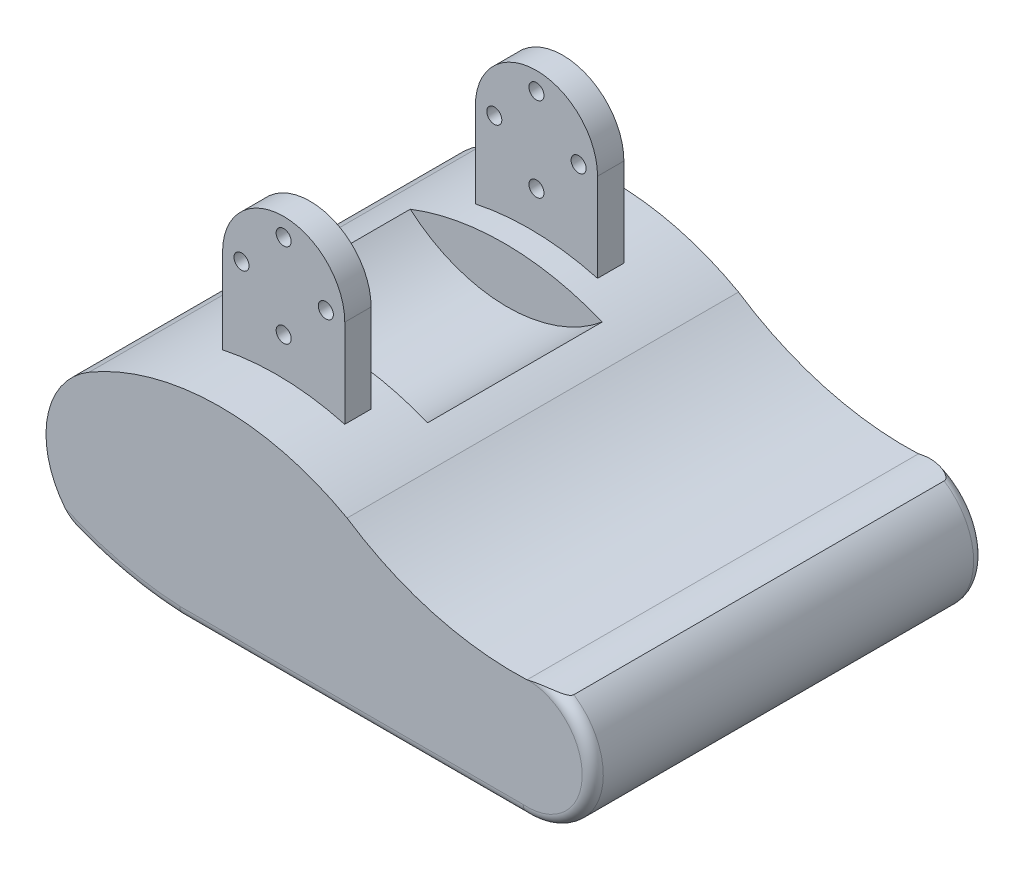
SolidWorks part; units mm, degrees
material "PLA"
ref_plane "Front Plane" through (0, 0, 0) normal (0, 0, 1) x (1, 0, 0)
ref_plane "Top Plane" through (0, 0, 0) normal (0, 1, 0) x (1, 0, 0)
ref_plane "Right Plane" through (0, 0, 0) normal (1, 0, 0) x (0, 0, -1)
sketch "Sketch1" plane through (0, 0, 0) normal (0, 0, 1) x (1, 0, 0)
  line L0 (-30, 0) -> (50, 0)
  line L1 (0, 0) -> (0, 25) construction
  line L2 (-30, 0) -> (-30, 25) construction
  line L3 (50, 0) -> (34.8329, 0) construction
  line L4 (-15, -2.8863) -> (48.734, -2.8863) construction
  line L5 (48.734, -2.8863) -> (48.734, 17.1137) construction
  line L6 (-15, -2.8863) -> (42.0254, -2.8863)
  line L7 (48.734, 17.1137) -> (42.7081, 17.1137) construction
  line L8 (-37.1668, 12.5) -> (-7.1668, 12.5) construction
  line L9 (-7.1668, 12.5) -> (12.8332, 12.5) construction
  line L10 (12.8332, 12.5) -> (12.8332, 25.4411) construction
  arc A0 (-30, 25) -> (-30, 0) centre (-22.6825, 12.5) ccw
  arc A7 (-30, 0) -> (-15, -2.8863) centre (-12.2067, 52.0503) ccw
  arc A8 (42.0254, -2.8863) -> (48.734, 17.1137) centre (42.7081, 8.0098) ccw
  arc A9 (48.734, 17.1137) -> (42.7081, 17.1137) centre (45.721, 5.4648) ccw
  arc A11 (-30, 25) -> (12.8332, 25.4411) centre (-8.1976, -12.2437) cw
  arc A12 (12.8332, 25.4411) -> (42.7081, 17.1137) centre (40.6286, 67.4056) ccw
  dimension "D5" = 20
  dimension "D6" = 30
  dimension "D1" = 30
  dimension "D2" = 50
  dimension "D3" = 25
  dimension "D4" = 25
  dimension "D7" = 20
extrude "Boss-Extrude1" add sketch "Sketch1" along normal blind 40 contours A9 A0 A7 L6 A8 region at (4.7955, 11.4421, 0)
sketch "Sketch3" plane through (0, 0, 40) normal (0, 0, 1) x (1, 0, 0)
  line L0 (-17.1668, 44.0921) -> (-17.1668, 16.5921)
  line L1 (3.1204, 44.0921) -> (3.1204, 16.5921)
  line L2 (-17.1668, 16.5921) -> (3.1204, 16.5921)
  arc A0 (3.1204, 44.0921) -> (-17.1668, 44.0921) centre (-7.0232, 44.0921) ccw
  dimension "D1" = 27.5
  dimension "D2" = 27.5
extrude "Boss-Extrude2" add sketch "Sketch3" along normal blind 3.175 and the other way blind 1.2
ref_plane "Plane1" through (0, 0, 20) normal (0, 0, -1) x (-1, 0, 0)
ref_plane "Plane2" through (0, 0, 34.4) normal (0, 0, 1) x (1, 0, 0)
sketch "Sketch4" plane through (0, 0, 34.4) normal (0, 0, 1) x (1, 0, 0)
  arc A0 (-23.7828, 27.9998) -> (8.0976, 27.7176) centre (-7.6768, 46.5915) ccw
  arc A1 (-17.1668, 29.9699) -> (-30, 25) centre (-8.1976, -12.2437) ccw construction
  arc A2 (12.8332, 25.4411) -> (3.1204, 29.4017) centre (-8.1976, -12.2437) ccw construction
  arc A3 (-23.7828, 27.9998) -> (8.0976, 27.7176) centre (-8.1976, -12.2437) cw
extrude "Cut-Extrude2" cut sketch "Sketch4" against normal blind 29
sketch "Sketch10" plane through (0, 0, 43.175) normal (0, 0, 1) x (1, 0, 0)
  line L0 (-7.0232, 54.2357) -> (-7.0232, 44.2357) construction
  arc A0 (3.1204, 44.0921) -> (-17.1668, 44.0921) centre (-7.0232, 44.0921) ccw construction
  circle A1 centre (-7.0232, 44.2357) radius 7 construction
  circle A2 centre (-7.0232, 51.2357) radius 1.25
  circle A3 centre (-0.0232, 44.2357) radius 1.25
  circle A4 centre (-7.0232, 37.2357) radius 1.25
  circle A5 centre (-14.0232, 44.2357) radius 1.25
  dimension "D2" = 14
  dimension "D3" = 2.5
  dimension "D1" = 10
extrude "Cut-Extrude4" cut sketch "Sketch10" against normal blind 10
sketch "Sketch6" plane through (0, 0, 40) normal (0, 0, 1) x (1, 0, 0)
  line L4 (3.1204, 29.4017) -> (3.1204, 16.5921)
  line L6 (3.1204, 16.5921) -> (-17.1668, 16.5921)
  line L7 (-15, -2.8863) -> (42.0254, -2.8863)
  line L11 (-15, -2.8863) -> (42.0254, -2.8863)
  line L13 (-17.1668, 16.5921) -> (-17.1668, 29.9699)
  arc A0 (8.0976, 27.7176) -> (-23.7828, 27.9998) centre (-8.1976, -12.2437) ccw construction
  arc A1 (8.0976, 27.7176) -> (-23.7828, 27.9998) centre (-8.1976, -12.2437) ccw
  arc A7 (12.8332, 25.4411) -> (3.1204, 29.4017) centre (-8.1976, -12.2437) ccw
  arc A8 (-17.1668, 29.9699) -> (-30, 25) centre (-8.1976, -12.2437) ccw
  arc A9 (-30, 25) -> (-30, 0) centre (-22.6825, 12.5) ccw
  arc A10 (-30, 0) -> (-15, -2.8863) centre (-12.2067, 52.0503) ccw
  arc A11 (42.0254, -2.8863) -> (48.734, 17.1137) centre (42.7081, 8.0098) ccw
  arc A12 (48.734, 17.1137) -> (42.7081, 17.1137) centre (45.721, 5.4648) ccw
  arc A13 (12.8332, 25.4411) -> (42.7081, 17.1137) centre (40.6286, 67.4056) ccw
  arc A14 (12.8332, 25.4411) -> (3.1204, 29.4017) centre (-8.1976, -12.2437) ccw
  arc A15 (-17.1668, 29.9699) -> (-30, 25) centre (-8.1976, -12.2437) ccw
  arc A16 (-30, 25) -> (-30, 0) centre (-22.6825, 12.5) ccw
  arc A17 (-30, 0) -> (-15, -2.8863) centre (-12.2067, 52.0503) ccw
  arc A18 (42.0254, -2.8863) -> (48.734, 17.1137) centre (42.7081, 8.0098) ccw
  arc A19 (48.734, 17.1137) -> (42.7081, 17.1137) centre (45.721, 5.4648) ccw
  arc A20 (12.8332, 25.4411) -> (42.7081, 17.1137) centre (40.6286, 67.4056) ccw
  arc M12 (12.8332, 25.4411) -> (3.1204, 29.4017) centre (-8.1976, -12.2437) ccw
  arc M16 (-17.1668, 29.9699) -> (-30, 25) centre (-8.1976, -12.2437) ccw
  arc M17 (-30, 25) -> (-30, 0) centre (-22.6825, 12.5) ccw
  arc M18 (-30, 0) -> (-15, -2.8863) centre (-12.2067, 52.0503) ccw
  line M19 (-15, -2.8863) -> (42.0254, -2.8863)
  arc M20 (42.0254, -2.8863) -> (48.734, 17.1137) centre (42.7081, 8.0098) ccw
  arc M21 (48.734, 17.1137) -> (42.7081, 17.1137) centre (45.721, 5.4648) ccw
  arc M22 (42.7081, 17.1137) -> (12.8332, 25.4411) centre (40.6286, 67.4056) cw
  line M23 (3.1204, 29.4017) -> (3.1204, 16.5921)
  line M24 (3.1204, 16.5921) -> (-17.1668, 16.5921)
  line M25 (-17.1668, 16.5921) -> (-17.1668, 29.9699)
  dimension "D1" = 0
extrude "Boss-Extrude3" add sketch "Sketch6" along normal blind 12.5 contours M12 M23 M24 M25 M16 M17 M18 M19 M20 M21 M22 | A1 M23 M25 M24 region at (6.4312, 9.7762, 40) region at (-7.0915, 23.5492, 40)
mirror "Mirror4" about plane through (0, 0, 20) normal (0, 0, -1) of "Boss-Extrude3"
sketch "Sketch5" plane through (0, -2.8863, 0) normal (0, -1, 0) x (1, 0, 0)
  line L4 (39.0254, 49.5) -> (-12, 49.5)
  line L5 (39.0254, 49.5) -> (-12, 49.5)
  line L6 (-12, -9.5) -> (39.0254, -9.5)
  line L7 (-12, -9.5) -> (39.0254, -9.5)
  line L9 (39.0254, -9.5) -> (39.0254, 49.5)
  line L11 (-12, 49.5) -> (-12, -9.5)
  line L13 (39.0254, -9.5) -> (39.0254, 49.5)
  line L15 (-12, 49.5) -> (-12, -9.5)
  dimension "D1" = 3
extrude "Cut-Extrude3" cut sketch "Sketch5" against normal blind 3.175
fillet "Fillet4" radius 1.75 6 edges at (53.0588, 4.5379, -12.5) (13.5127, -2.8863, -12.5) (-22.6007, -1.9664, -12.5) (-22.6007, -1.9664, 52.5) (53.0588, 4.5379, 52.5) (13.5127, -2.8863, 52.5)
mirror "Mirror5" about plane through (0, 0, 20) normal (0, 0, -1) of "Boss-Extrude2", "Cut-Extrude4"
